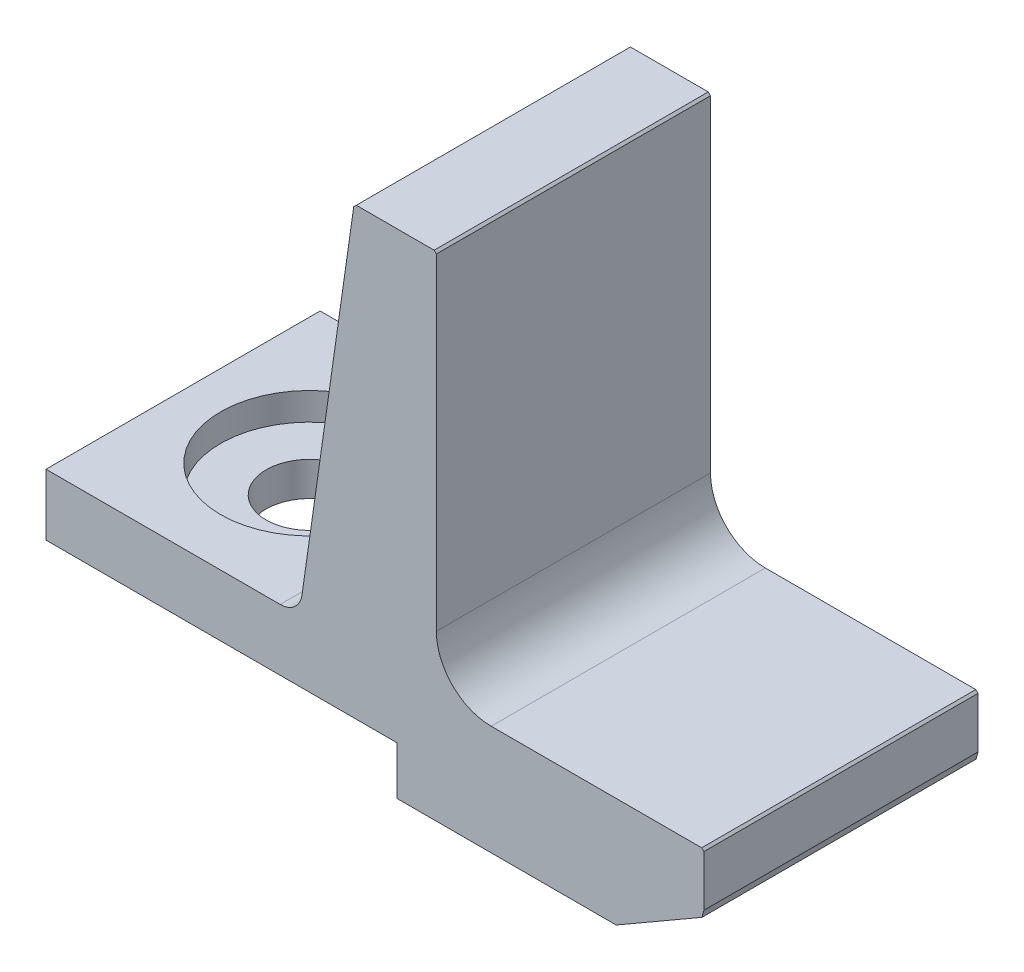
SolidWorks part; units mm, degrees
ref_plane "Front Plane" through (0, 0, 0) normal (0, 0, 1) x (1, 0, 0)
ref_plane "Top Plane" through (0, 0, 0) normal (0, 1, 0) x (1, 0, 0)
ref_plane "Right Plane" through (0, 0, 0) normal (1, 0, 0) x (0, 0, -1)
sketch "Sketch1" plane through (0, 0, 0) normal (0, 0, 1) x (1, 0, 0)
  line L0 (0, 0) -> (30.988, 0)
  line L1 (30.988, 0) -> (30.988, -12.7)
  line L2 (30.988, -12.7) -> (-4.572, -12.7)
  line L3 (-45.212, -7.112) -> (-45.212, 0)
  line L4 (-45.212, 0) -> (-15.875, 0)
  line L5 (-15.875, 0) -> (-9.525, 44.45)
  line L6 (-9.525, 44.45) -> (0, 44.45)
  line L7 (0, 44.45) -> (0, 0)
  line L8 (-4.572, -12.7) -> (-4.572, -7.112)
  line L9 (-4.572, -7.112) -> (-45.212, -7.112)
  dimension "D1" = 30.988
  dimension "D2" = 44.45
  dimension "D3" = 12.7
  dimension "D4" = 76.2
  dimension "D5" = 9.525
  dimension "D6" = 5.588
  dimension "D7" = 40.64
  dimension "D8" = 15.875
extrude "Boss-Extrude1" add sketch "Sketch1" along normal blind 31.75
hole_wizard "CBORE for 3/8 Binding Head Machine Screw1" positions "Sketch6" profile "Sketch3" counterbore size "3/8" standard "ANSI Inch" end condition through all
sketch "Sketch6" plane through (0, 0, 0) normal (0, 1, 0) x (1, 0, 0)
  line L0 (-15.875, 0) -> (-45.212, 0) construction
  line L1 (-45.212, -31.75) -> (-45.212, 0) construction
  point P0 (-30.5435, -15.875)
  point P5 (-30.5435, 0)
  point P8 (-45.212, -15.875)
sketch "Sketch3" plane through (-30.5435, 0, 15.875) normal (1, 0, 0) x (0, 0, 1)
  line L0 (0, 0) -> (0, 12.7)
  line L1 (0, 12.7) -> (5.0419, 12.7)
  line L3 (5.0419, 12.7) -> (5.0419, 3.175)
  line L4 (10.3187, 3.175) -> (5.0419, 3.175)
  line L5 (10.3187, 3.175) -> (10.3187, 0)
  line L7 (10.3187, 0) -> (0, 0)
  line L11 (0, 0) -> (0, 107.95) construction
  dimension "Thru Hole Dia." = 10.0838
  dimension "Thru Hole Depth" = 12.7
  dimension "C'Bore Depth" = 3.175
chamfer "Chamfer1" distance 10.16 angle 30 1 edges at (30.988, -12.7, 15.875) first distance on face at (13.208, -12.7, 15.875)
fillet "Fillet1" radius 2.54 1 edges at (-15.875, 0, 15.875)
fillet "Fillet2" radius 6.35 1 edges at (0, 0, 15.875)
chamfer "Chamfer2" distance 0.254 angle 45 4 edges at (30.988, -6.8341, 15.875) (30.988, 0, 15.875) (0, 44.45, 15.875) (-9.525, 44.45, 15.875) first distance on face at (25.908, -9.7671, 15.875) first distance on face at (30.988, -3.4171, 15.875) first distance on face at (-4.7625, 44.45, 15.875)
